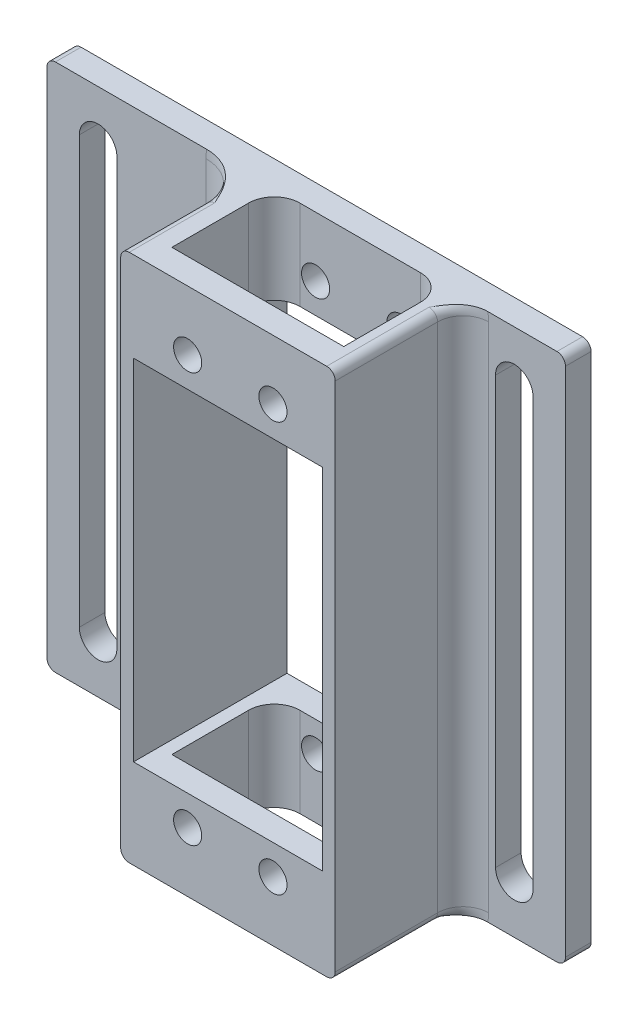
SolidWorks part; units mm, degrees
ref_plane "前视基准面" through (0, 0, 0) normal (0, 0, 1) x (1, 0, 0)
ref_plane "上视基准面" through (0, 0, 0) normal (0, 1, 0) x (1, 0, 0)
ref_plane "右视基准面" through (0, 0, 0) normal (1, 0, 0) x (0, 0, -1)
sketch "草图1" plane through (0, 0, 0) normal (0, 0, 1) x (1, 0, 0)
  line L5 (-25.8, 6) -> (35, 6)
  line L6 (-25.8, 6) -> (-25.8, -56)
  line L7 (-25.8, -56) -> (35, -56)
  line L8 (35, 6) -> (35, -56)
  line L10 (26.8, 0) -> (26.8, -50)
  line L11 (31.2, 0) -> (31.2, -50)
  line L13 (-22, 0) -> (-22, -50)
  line L14 (-17.6, 0) -> (-17.6, -50)
  arc A1 (31.2, 0) -> (26.8, 0) centre (29, 0) ccw
  arc A2 (26.8, -50) -> (31.2, -50) centre (29, -50) ccw
  arc A4 (-17.6, 0) -> (-22, 0) centre (-19.8, 0) ccw
  arc A5 (-22, -50) -> (-17.6, -50) centre (-19.8, -50) ccw
  dimension "D3" = 6
  dimension "D4" = 6
  dimension "D5" = 6
  dimension "D6" = 2
  dimension "D8" = 60.8
  dimension "D2" = 50
  dimension "D10" = 4.4
extrude "凸台-拉伸1" add sketch "草图1" along normal blind 3
sketch "草图2" plane through (0, 0, 3) normal (0, 0, 1) x (1, 0, 0)
  line L0 (35, 6) -> (-25.8, 6) construction
  line L6 (-2.15, 6) -> (23, 6)
  line L7 (-2.15, 6) -> (-2.15, -56)
  line L8 (-2.15, -56) -> (23, -56)
  line L9 (23, 6) -> (23, -56)
  line L13 (35, -56) -> (35, 6) construction
  circle A0 centre (5.7, -1) radius 1.65
  circle A1 centre (15.7, -1) radius 1.65
  circle A2 centre (15.7, -49) radius 1.65
  circle A3 centre (5.7, -49) radius 1.65
  dimension "D4" = 7
  dimension "D5" = 62
  dimension "D6" = 25.15
  dimension "D7" = 7
  dimension "D3" = 7.85
  dimension "D1" = 10
  dimension "D2" = 48
  dimension "D8" = 62
  dimension "D9" = 12
extrude "凸台-拉伸2" add sketch "草图2" along normal blind 15
sketch "草图4" plane through (0, 0, 18) normal (0, 0, 1) x (1, 0, 0)
  line L1 (-0.65, -4.5) -> (21.5, -4.5)
  line L2 (-0.65, -4.5) -> (-0.65, -45.5)
  line L3 (-0.65, -45.5) -> (21.5, -45.5)
  line L4 (21.5, -4.5) -> (21.5, -45.5)
  line L5 (-2.15, 6) -> (-2.15, -56) construction
  line L6 (23, -56) -> (23, 6) construction
  line L7 (23, 6) -> (-2.15, 6) construction
  line L8 (-2.15, -56) -> (23, -56) construction
  circle A0 centre (5.7, -1) radius 1.65
  circle A1 centre (5.7, -49) radius 1.65
  circle A2 centre (15.7, -49) radius 1.65
  circle A3 centre (15.7, -1) radius 1.65
  dimension "D1" = 1.5
  dimension "D2" = 1.5
  dimension "D3" = 10.5
  dimension "D4" = 10.5
extrude "切除-拉伸4" cut sketch "草图4" against normal blind 45
fillet "圆角1" radius 1 8 edges at (-25.8, -56, 1.5) (35, -56, 1.5) (35, 6, 1.5) (-25.8, 6, 1.5) (-2.15, 6, 10.5) (23, 6, 10.5) (23, -56, 10.5) (-2.15, -56, 10.5)
fillet "圆角2" radius 5 3 edges at (-1.8571, 5.7071, 3) (-1.8571, -55.7071, 3) (-2.15, -25, 3)
sketch "草图5" plane through (0, -56, 0) normal (0, -1, 0) x (-1, 0, 0)
  line L0 (1.15, -18) -> (1.15, -8) construction
  line L1 (-0.85, -15) -> (-21, -15)
  line L2 (-0.85, -15) -> (-0.85, -3)
  line L3 (-0.85, -3) -> (-21, -3)
  line L4 (-21, -15) -> (-21, -3)
  line L5 (-23, -18) -> (-23, -3) construction
  line L6 (1.15, -18) -> (-22, -18) construction
  dimension "D1" = 2
  dimension "D2" = 2
  dimension "D3" = 3
  dimension "D4" = 3
extrude "切除-拉伸5" cut sketch "草图5" against normal blind 70
fillet "圆角3" radius 3 4 edges at (0.85, 0.75, 3) (21, 0.75, 3) (21, -50.75, 3) (0.85, -50.75, 3)
fillet "圆角4" radius 3 3 edges at (22.7071, -55.7071, 3) (22.7071, 5.7071, 3) (23, -25, 3)
